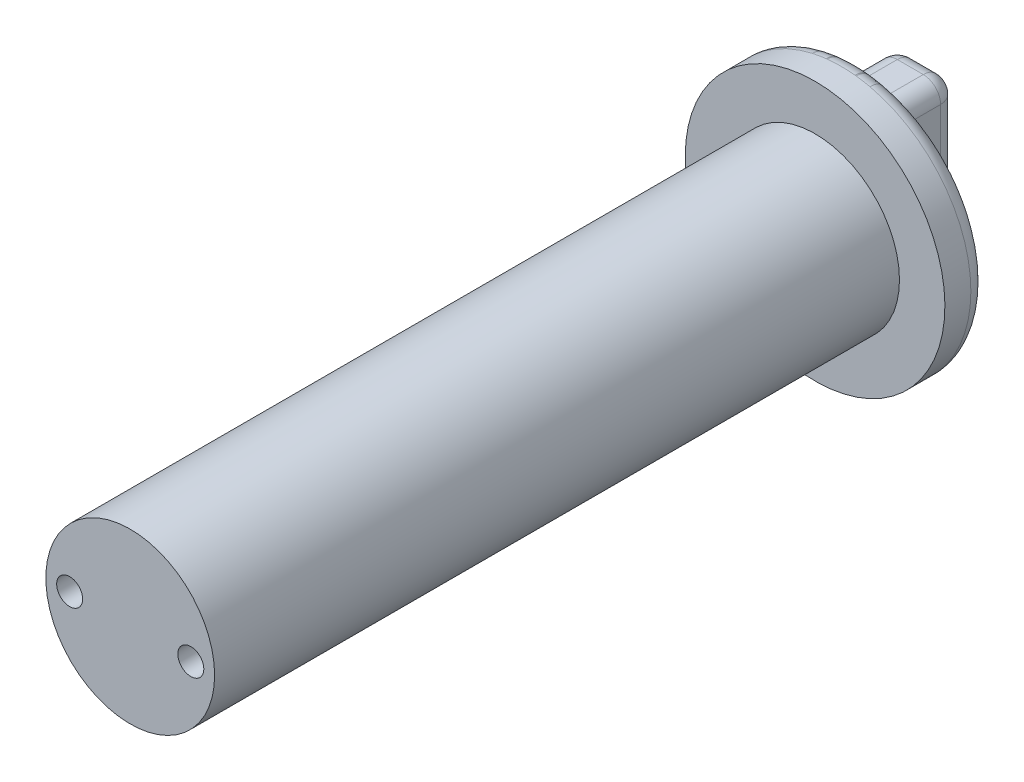
SolidWorks part; units mm, degrees
material "6061 Alloy"
ref_plane "Front Plane" through (0, 0, 0) normal (0, 0, 1) x (1, 0, 0)
ref_plane "Top Plane" through (0, 0, 0) normal (0, 1, 0) x (1, 0, 0)
ref_plane "Right Plane" through (0, 0, 0) normal (1, 0, 0) x (0, 0, -1)
sketch "Sketch1" plane through (0, 0, 0) normal (0, 0, 1) x (1, 0, 0)
  circle A0 centre (0, 0) radius 9.75
  dimension "D1" = 19.5
extrude "Boss-Extrude1" add sketch "Sketch1" along normal blind 79.125
sketch "Sketch2" plane through (0, 0, 0) normal (0, 0, -1) x (-1, 0, 0)
  circle A0 centre (0, 0) radius 15
  dimension "D1" = 30
extrude "Boss-Extrude2" add sketch "Sketch2" along normal blind 5
sketch "Sketch3" plane through (0, 0, -5) normal (0, 0, -1) x (-1, 0, 0)
  line L1 (-3.5, 10.9245) -> (3.5, 10.9245)
  line L2 (-3.5, 10.9245) -> (-3.5, -10.9245)
  line L3 (-3.5, -10.9245) -> (3.5, -10.9245)
  line L4 (3.5, 10.9245) -> (3.5, -10.9245)
  line L5 (0, -10.9245) -> (0, 10.9245) construction
  line L6 (-3.5, 0) -> (3.5, 0) construction
  point P0 (0, 0)
  dimension "D1" = 7
extrude "Boss-Extrude4" add sketch "Sketch3" along normal blind 8
fillet "Fillet1" radius 2 12 edges at (-3.5, 0, -5) (-3.5, 10.9245, -9) (0, 10.9245, -5) (3.5, 10.9245, -9) (3.5, 0, -5) (3.5, -10.9245, -9) (-3.5, -10.9245, -9) (0, -10.9245, -5) (0, -10.9245, -13) (3.5, 0, -13) (0, 10.9245, -13) (-3.5, 0, -13)
fillet "Fillet2" radius 2 1 edges at (-15, 0, -5)
sketch "Sketch4" plane through (0, 0, 79.125) normal (0, 0, 1) x (1, 0, 0)
  line L0 (0, 0) -> (-7, 0) construction
  line L1 (0, 0) -> (0, -4.7782) construction
  circle A0 centre (-7, 0) radius 1.5
  circle A1 centre (7, 0) radius 1.5
  dimension "D1" = 3
  dimension "D2" = 7
extrude "M4_DRILL" cut sketch "Sketch4" against normal blind 8
